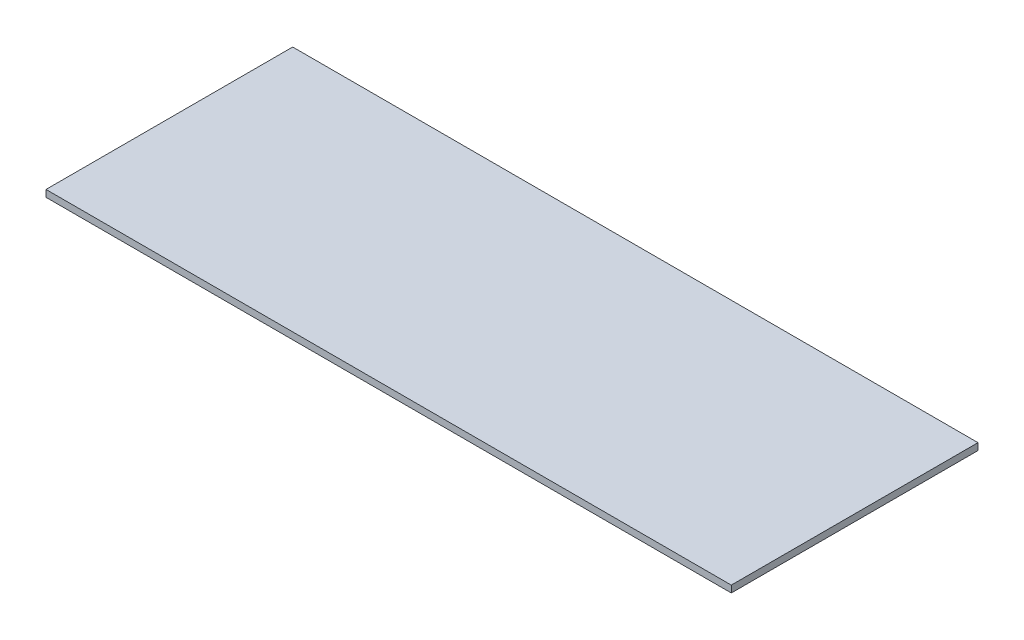
SolidWorks part; units mm, degrees
ref_plane "Front Plane" through (0, 0, 0) normal (0, 0, 1) x (1, 0, 0)
ref_plane "Top Plane" through (0, 0, 0) normal (0, 1, 0) x (1, 0, 0)
ref_plane "Right Plane" through (0, 0, 0) normal (1, 0, 0) x (0, 0, -1)
sketch "Sketch1" plane through (0, 0, 0) normal (0, 1, 0) x (1, 0, 0)
  line L1 (-317.5, -114.3) -> (317.5, -114.3)
  line L2 (-317.5, -114.3) -> (-317.5, 114.3)
  line L3 (-317.5, 114.3) -> (317.5, 114.3)
  line L4 (317.5, -114.3) -> (317.5, 114.3)
  line L5 (-317.5, -114.3) -> (317.5, 114.3) construction
  line L6 (-317.5, 114.3) -> (317.5, -114.3) construction
  point P0 (0, 0)
  dimension "D1" = 635
  dimension "D2" = 228.6
extrude "Boss-Extrude1" add sketch "Sketch1" along normal blind 6.35
